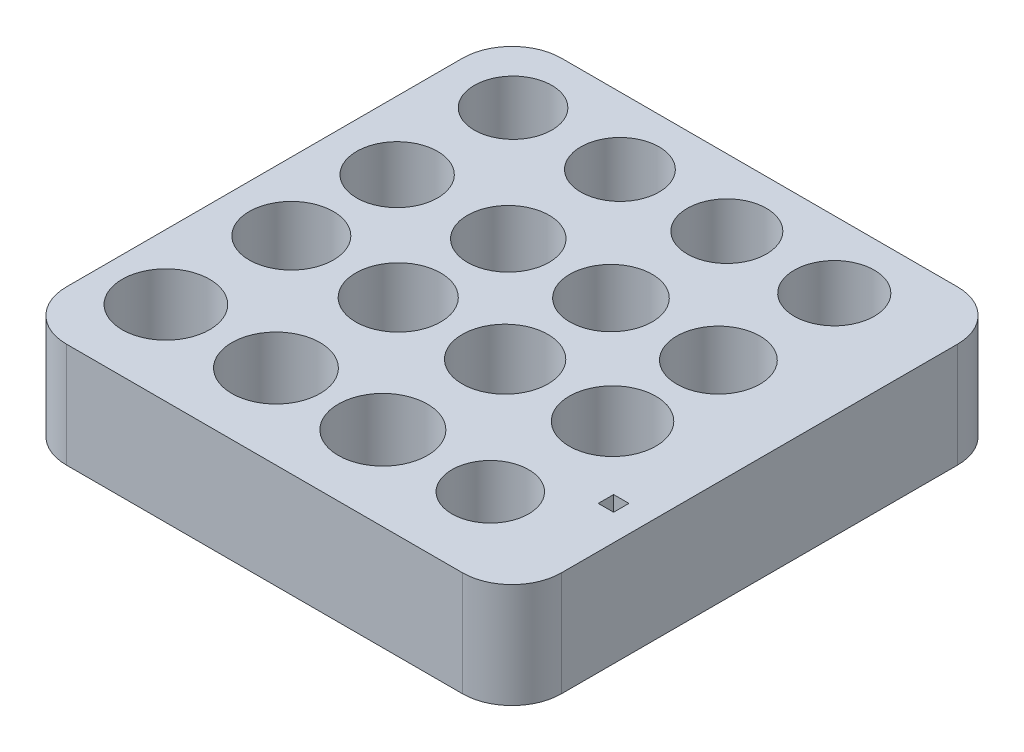
SolidWorks part; units mm, degrees
ref_plane "Front Plane" through (0, 0, 0) normal (0, 0, 1) x (1, 0, 0)
ref_plane "Top Plane" through (0, 0, 0) normal (0, 1, 0) x (1, 0, 0)
ref_plane "Right Plane" through (0, 0, 0) normal (1, 0, 0) x (0, 0, -1)
sketch "Sketch1" plane through (0, 0, 0) normal (0, 1, 0) x (1, 0, 0)
  line L1 (3, 0) -> (27, 0)
  line L2 (0, 3) -> (0, 27)
  line L3 (3, 30) -> (27, 30)
  line L4 (30, 3) -> (30, 27)
  arc A0 (3, 0) -> (0, 3) centre (3, 3) cw
  arc A1 (27, 0) -> (30, 3) centre (27, 3) ccw
  arc A2 (27, 30) -> (30, 27) centre (27, 27) cw
  arc A3 (0, 27) -> (3, 30) centre (3, 27) cw
  point P7 (0, 0)
  point P10 (30, 0)
  point P13 (30, 30)
  point P16 (0, 30)
  dimension "D3" = 3
  dimension "D1" = 30
  dimension "D2" = 30
extrude "Boss-Extrude1" add sketch "Sketch1" along normal blind 6.35
sketch "Sketch2" plane through (0, 6.35, 0) normal (0, 1, 0) x (1, 0, 0)
  line L1 (27.4728, 8.6834) -> (28.4026, 8.6834)
  line L2 (27.4728, 8.6834) -> (27.4728, 7.7536)
  line L3 (27.4728, 7.7536) -> (28.4026, 7.7536)
  line L4 (28.4026, 8.6834) -> (28.4026, 7.7536)
  circle A0 centre (4.1304, 25.9337) radius 2.35
  circle A1 centre (17.0841, 25.9337) radius 2.4
  circle A2 centre (4.1304, 18.9118) radius 2.45
  circle A3 centre (17.0841, 18.9118) radius 2.5
  circle A4 centre (10.6073, 25.9337) radius 2.375
  circle A5 centre (23.5931, 25.9337) radius 2.425
  circle A6 centre (10.8638, 18.9118) radius 2.475
  circle A7 centre (23.5931, 18.9118) radius 2.525
  circle A8 centre (4.1304, 12.499) radius 2.55
  circle A9 centre (10.6073, 12.499) radius 2.575
  circle A10 centre (17.0841, 12.499) radius 2.6
  circle A11 centre (23.5931, 12.499) radius 2.625
  circle A12 centre (3.938, 5.0923) radius 2.65
  circle A13 centre (10.6073, 5.0923) radius 2.675
  circle A14 centre (17.0841, 5.0923) radius 2.7
  circle A15 centre (23.5931, 5.0923) radius 2.325
  dimension "D1" = 4.7
  dimension "D2" = 4.8
  dimension "D3" = 4.9
  dimension "D4" = 5
  dimension "D5" = 4.75
  dimension "D6" = 4.85
  dimension "D7" = 4.95
  dimension "D8" = 5.05
  dimension "D9" = 5.1
  dimension "D10" = 5.15
  dimension "D11" = 5.2
  dimension "D12" = 5.25
  dimension "D13" = 5.3
  dimension "D14" = 5.35
  dimension "D15" = 5.4
  dimension "D16" = 4.65
extrude "Cut-Extrude1" cut sketch "Sketch2" against normal blind 6.35
